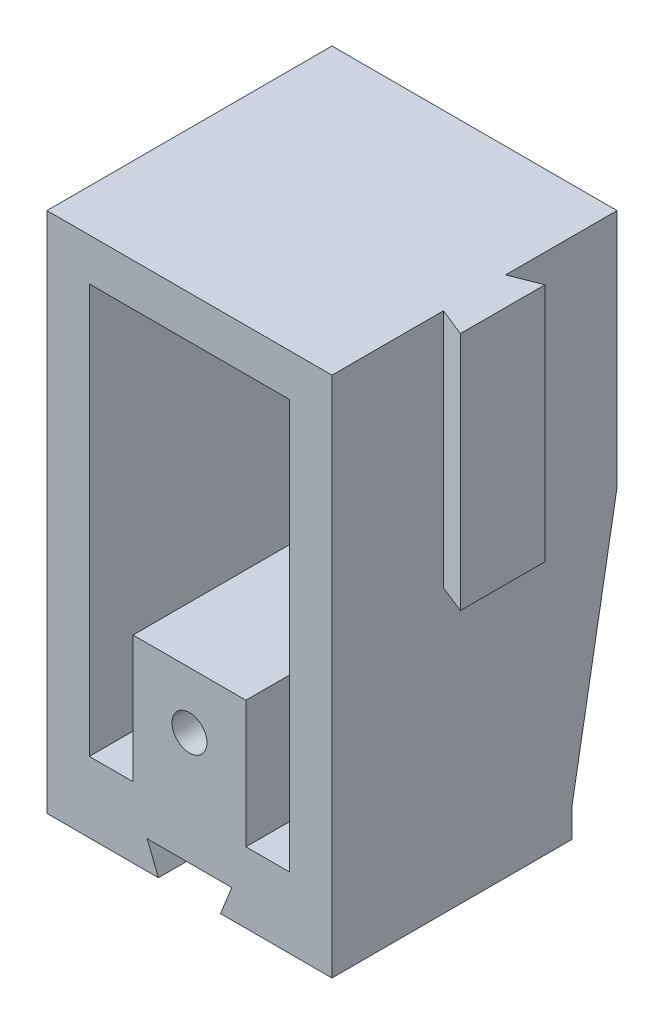
SolidWorks part; units mm, degrees
ref_plane "Front Plane" through (0, 0, 0) normal (0, 0, 1) x (1, 0, 0)
ref_plane "Top Plane" through (0, 0, 0) normal (0, 1, 0) x (1, 0, 0)
ref_plane "Right Plane" through (0, 0, 0) normal (1, 0, 0) x (0, 0, -1)
sketch "Sketch1" plane through (0, 0, 0) normal (0, 1, 0) x (1, 0, 0)
  line L0 (25.25, 5.5) -> (30.25, 7.5)
  line L1 (-25.25, 25.25) -> (25.25, 25.25)
  line L2 (-25.25, 25.25) -> (-25.25, -25.25)
  line L3 (-25.25, -25.25) -> (25.25, -25.25)
  line L4 (25.25, 25.25) -> (25.25, -25.25)
  line L5 (-25.25, 25.25) -> (25.25, -25.25) construction
  line L6 (-25.25, -25.25) -> (25.25, 25.25) construction
  line L7 (30.25, 7.5) -> (30.25, -7.5)
  line L8 (30.25, -7.5) -> (25.25, -5.5)
  line L9 (25.25, 25.25) -> (30.25, 7.5) construction
  line L10 (30.25, -7.5) -> (25.25, -25.25) construction
  line L11 (25.25, 25.25) -> (25.25, -25.25)
  line L12 (25.25, 5.5) -> (25.25, -5.5)
  point P0 (0, 0)
  dimension "D1" = 50.5
  dimension "D2" = 50.5
  dimension "D3" = 50.5
  dimension "D4" = 15
  dimension "D5" = 5
  dimension "D6" = 2
extrude "Boss-Extrude1" add sketch "Sketch1" along normal blind 42.5 contours L1 L11 L3 L4 | L8 L7 L0 L4 | L11 L1 L2 L3 region at (0, 0, 0) region at (27.8782, 0, 0)
extrude "Boss-Extrude2" add sketch "Sketch1<3>" against normal blind 50 contours L11 L1 L2 L3 region at (0, 0, 0)
sketch "Sketch1<3>" plane through (0, 0, 0) normal (0, 1, 0) x (1, 0, 0) same geometry as "Sketch1"
sketch "Sketch2" plane through (0, 0, -25.25) normal (0, 0, -1) x (-1, 0, 0)
  line L0 (-5.5, -50) -> (-7.5, -45)
  line L1 (25.25, -50) -> (-25.25, -50) construction
  line L2 (-7.5, -45) -> (7.5, -45)
  line L3 (7.5, -45) -> (5.5, -50)
  line L4 (5.5, -50) -> (-5.5, -50)
  line L5 (-7.5, -45) -> (-25.25, -50) construction
  line L6 (7.5, -45) -> (25.25, -50) construction
  dimension "D1" = 15
  dimension "D2" = 5
  dimension "D3" = 2
extrude "Cut-Extrude1" cut sketch "Sketch2" against normal blind 70
sketch "Sketch3" plane through (25.25, 0, 0) normal (1, 0, 0) x (0, 0, -1)
  line L1 (25.25, -50) -> (-25.25, -50) construction
  line L2 (17.25, -50) -> (25.25, -50)
  line L3 (25.25, -50) -> (25.25, 42.5) construction
  line L4 (25.25, -50) -> (25.25, 0)
  line L5 (17.25, -50) -> (17.25, -45)
  line L6 (17.25, -45) -> (25.25, 0)
  line L7 (7.5, 0) -> (25.25, 0) construction
  line L8 (7.5, 0) -> (-7.5, 0) construction
  line L9 (25.25, 42.5) -> (25.25, -50) construction
  line L10 (-25.25, 42.5) -> (-25.25, -50) construction
  dimension "D1" = 42.5
  dimension "D2" = 5
extrude "Cut-Extrude2" cut sketch "Sketch3" against normal blind 70
sketch "Sketch4" plane through (0, 0, 25.25) normal (0, 0, 1) x (1, 0, 0)
  line L1 (-25.25, -25) -> (25.25, -25) construction
  line L2 (-25.25, 42.5) -> (-25.25, -50) construction
  line L3 (5.5, -50) -> (25.25, -50) construction
  line L4 (25.25, 42.5) -> (25.25, -50) construction
  circle A0 centre (0, -25) radius 3.1
  dimension "D1" = 6.2
  dimension "D2" = 25
extrude "Cut-Extrude3" cut sketch "Sketch4" against normal blind 70
sketch "Sketch5" plane through (0, 0, 25.25) normal (0, 0, 1) x (1, 0, 0)
  line L0 (-25.25, 42.5) -> (25.25, 42.5) construction
  line L1 (-17.75, 35) -> (17.75, 35)
  line L2 (-17.75, 35) -> (-17.75, -15)
  line L3 (-17.75, -15) -> (17.75, -15)
  line L4 (17.75, 35) -> (17.75, -15)
  line L5 (-25.25, 42.5) -> (-25.25, -50) construction
  line L6 (25.25, 42.5) -> (25.25, -50) construction
  line L7 (-7.5, -45) -> (7.5, -45) construction
  line L8 (-17.75, -15) -> (-10, -15)
  line L9 (-17.75, -15) -> (-17.75, -37.5)
  line L10 (-17.75, -37.5) -> (-10, -37.5)
  line L11 (-10, -15) -> (-10, -37.5)
  line L12 (17.75, -15) -> (10, -15)
  line L13 (17.75, -15) -> (17.75, -37.5)
  line L14 (17.75, -37.5) -> (10, -37.5)
  line L15 (10, -15) -> (10, -37.5)
  circle A0 centre (0, -25) radius 3.1 construction
  dimension "D8" = 10
  dimension "D1" = 7.5
  dimension "D2" = 7.5
  dimension "D3" = 7.5
  dimension "D4" = 10
  dimension "D5" = 7.5
  dimension "D6" = 7.5
  dimension "D7" = 10
extrude "Cut-Extrude4" cut sketch "Sketch5" against normal blind 55 contours L4 L1 L2 L3 | L11 L3 L9 L10 | L3 L15 L14 L13 region at (0, 10, 25.25) region at (-13.875, -26.25, 25.25) region at (13.875, -26.25, 25.25)
